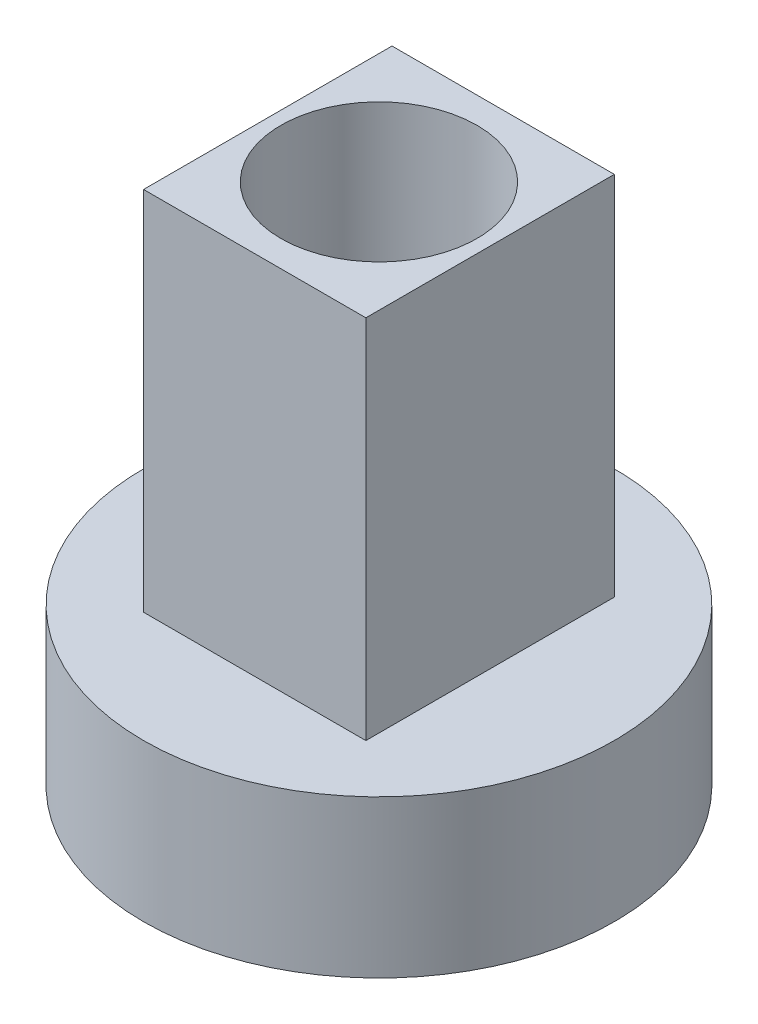
SolidWorks part; units mm, degrees
ref_plane "Спереди" through (0, 0, 0) normal (0, 0, 1) x (1, 0, 0)
ref_plane "Сверху" through (0, 0, 0) normal (0, 1, 0) x (1, 0, 0)
ref_plane "Справа" through (0, 0, 0) normal (1, 0, 0) x (0, 0, -1)
sketch "Эскиз2" plane through (0, 0, 0) normal (0, 1, 0) x (1, 0, 0)
  circle A0 centre (0, 0) radius 90
extrude "Бобышка - Цилиндр" add sketch "Эскиз2" along normal blind 60
sketch "Эскиз4" plane through (0, 60, 0) normal (0, 1, 0) x (1, 0, 0)
  line L1 (-42.5, 47.5) -> (42.5, 47.5)
  line L2 (-42.5, 47.5) -> (-42.5, -47.5)
  line L3 (-42.5, -47.5) -> (42.5, -47.5)
  line L4 (42.5, 47.5) -> (42.5, -47.5)
  line L5 (-42.5, 47.5) -> (42.5, -47.5) construction
  line L6 (-42.5, -47.5) -> (42.5, 47.5) construction
  point P1 (0, 0)
extrude "Бобышка - Паралеллограмм" add sketch "Эскиз4" along normal blind 140
sketch "Эскиз5" plane through (0, 200, 0) normal (0, 1, 0) x (1, 0, 0)
  circle A0 centre (0, 0) radius 37.5
extrude "Вырез центральный" cut sketch "Эскиз5" against normal through all
shell "Оболочка" thickness 3 removed face at (0, 0, 37.5)
